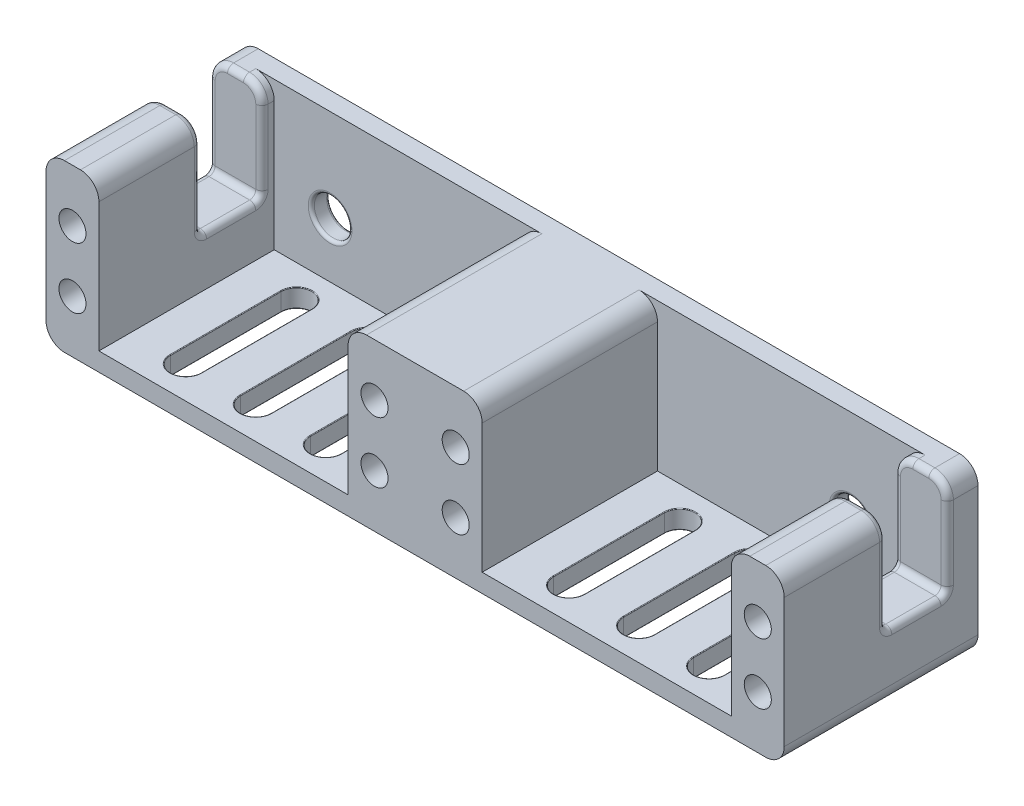
SolidWorks part; units mm, degrees
ref_plane "Front Plane" through (0, 0, 0) normal (0, 0, 1) x (1, 0, 0)
ref_plane "Top Plane" through (0, 0, 0) normal (0, 1, 0) x (1, 0, 0)
ref_plane "Right Plane" through (0, 0, 0) normal (1, 0, 0) x (0, 0, -1)
sketch "Sketch1" plane through (0, 0, 0) normal (0, 1, 0) x (1, 0, 0)
  line L0 (0, 0) -> (60, 0)
  line L6 (60, -31.5) -> (0, -31.5)
  line L7 (0, -31.5) -> (0, -26.5)
  line L9 (0, -26.5) -> (0, -3)
  line L11 (0, -3) -> (0, 0)
  line L12 (60, 0) -> (60, -31.5)
  dimension "D1" = 23.5
  dimension "D2" = 5
  dimension "D3" = 60
  dimension "D4" = 31.5
  dimension "D6" = 3
extrude "Boss-Extrude1" add sketch "Sketch1" along normal blind 27
sketch "Sketch2" plane through (0, 0, 31.5) normal (0, 0, 1) x (1, 0, 0)
  line L0 (0, 27) -> (0, 0) construction
  line L1 (0, 13.5) -> (60, 13.5) construction
  line L3 (60, 27) -> (60, 0) construction
  circle A0 centre (4.3, 18.45) radius 2.2
  circle A1 centre (4.3, 8.55) radius 2.2
  circle A2 centre (53.4, 18.45) radius 2.2
  circle A3 centre (53.4, 8.55) radius 2.2
  point P10 (28.85, 13.5)
  dimension "D1" = 4.3
  dimension "D2" = 4.4
  dimension "D3" = 9.9
  dimension "D4" = 4.95
  dimension "D8" = 4.4
  dimension "D9" = 9.9
  dimension "D10" = 49.1
  dimension "D11" = 4.95
  dimension "D12" = 4.4
extrude "Cut-Extrude1" cut sketch "Sketch2" against normal blind 5
sketch "Sketch4" plane through (0, 0, 31.5) normal (0, 0, 1) x (1, 0, 0)
  line L0 (49.1, 3) -> (8.6, 3)
  line L1 (49.1, 3) -> (49.1, 24)
  line L2 (49.1, 24) -> (8.6, 24)
  line L3 (8.6, 3) -> (8.6, 24)
  line L4 (0, 13.5) -> (60, 13.5) construction
  line L5 (0, 27) -> (0, 0) construction
  line L6 (60, 27) -> (60, 0) construction
  line L7 (8.6, 13.5) -> (49.1, 13.5) construction
  circle A0 centre (4.3, 18.45) radius 2.2 construction
  dimension "D1" = 4.3
  dimension "D2" = 40.5
  dimension "D3" = 21
extrude "Cut-Extrude2" cut sketch "Sketch4" against normal blind 28.5
sketch "Sketch5" plane through (0, 0, 31.5) normal (0, 0, 1) x (1, 0, 0)
  line L0 (8.6, 24) -> (8.6, 27)
  line L1 (8.6, 24) -> (49.1, 24)
  line L2 (8.6, 27) -> (49.1, 27)
  line L3 (49.1, 24) -> (49.1, 27)
  line L4 (0, 27) -> (60, 27) construction
  line L5 (49.1, 3) -> (49.1, 24) construction
  line L6 (49.1, 3) -> (49.1, 24) construction
extrude "Cut-Extrude4" cut sketch "Sketch5" against normal blind 28.5
sketch "Sketch10" plane through (0, 3, 0) normal (0, 1, 0) x (1, 0, 0)
  line L0 (28.85, -3) -> (28.85, -31.5) construction
  line L1 (49.1, -3) -> (8.6, -3) construction
  line L2 (8.6, -31.5) -> (49.1, -31.5) construction
  line L3 (8.6, -17.25) -> (49.1, -17.25) construction
  line L4 (8.6, -3) -> (8.6, -31.5) construction
  line L5 (49.1, -3) -> (49.1, -31.5) construction
  line L6 (28.85, -17.25) -> (26.35, -26.25) construction
  line L8 (31.35, -26.25) -> (31.35, -8.25)
  line L10 (26.35, -26.25) -> (26.35, -8.25)
  line L11 (28.85, -17.25) -> (26.35, -8.25) construction
  line L12 (31.35, -8.25) -> (28.85, -17.25) construction
  line L13 (31.35, -26.25) -> (28.85, -17.25) construction
  line L14 (42.73, -26.25) -> (42.73, -8.25)
  line L15 (37.73, -26.25) -> (37.73, -8.25)
  line L16 (40.23, -5.75) -> (40.23, -28.75) construction
  line L17 (19.97, -26.25) -> (19.97, -8.25)
  line L18 (14.97, -26.25) -> (14.97, -8.25)
  arc A0 (31.35, -8.25) -> (26.35, -8.25) centre (28.85, -8.25) ccw
  arc A1 (31.35, -26.25) -> (26.35, -26.25) centre (28.85, -26.25) cw
  arc A2 (42.73, -8.25) -> (37.73, -8.25) centre (40.23, -8.25) ccw
  arc A3 (42.73, -26.25) -> (37.73, -26.25) centre (40.23, -26.25) cw
  arc A4 (14.97, -26.25) -> (19.97, -26.25) centre (17.47, -26.25) ccw
  arc A5 (14.97, -8.25) -> (19.97, -8.25) centre (17.47, -8.25) cw
  point P12 (28.85, -17.25)
  point P20 (31.35, -17.25)
  point P22 (26.35, -17.25)
  dimension "D3" = 2.5
  dimension "D1" = 5
  dimension "D2" = 18
  dimension "D5" = 11.38
  dimension "D4" = 2
extrude "Cut-Extrude7" cut sketch "Sketch10" along direction (0, -1, 0) on the side against the normal up to surface (3 mm away) up to face at (30, 0, 15.75)
sketch "Sketch6" plane through (8.6, 0, 0) normal (1, 0, 0) x (0, 0, -1)
  line L5 (-15, 27) -> (-5, 27)
  line L6 (-15, 27) -> (-15, 11)
  line L7 (-5, 27) -> (-5, 11)
  line L8 (-15, 11) -> (-5, 11)
  line L9 (-3, 27) -> (-31.5, 27) construction
  line L10 (-3, 27) -> (-3, 3) construction
  line L11 (-31.5, 15) -> (-3, 15) construction
  line L12 (-31.5, 27) -> (-31.5, 3) construction
  dimension "D3" = 2
  dimension "D4" = 10
  dimension "D5" = 4
extrude "Cut-Extrude5" cut sketch "Sketch6" against normal blind 28.5
fillet "Fillet1" radius 3 6 edges at (0, 0, 15.75) (0, 27, 2.5) (8.6, 27, 4) (0, 27, 23.25) (8.6, 27, 23.25) (49.1, 27, 17.25)
sketch "Sketch11" plane through (0, 0, 31.5) normal (0, 0, 1) x (1, 0, 0)
  line L0 (60, 13.5) -> (49.1, 13.5) construction
  line L1 (60, 27) -> (60, 0) construction
  line L2 (49.1, 3) -> (49.1, 24) construction
  line L3 (60, 24) -> (60, 3)
  line L4 (60, 24) -> (58.5, 24)
  line L5 (60, 3) -> (58.5, 3)
  line L6 (58.5, 24) -> (58.5, 3)
  line L7 (52.1, 27) -> (60, 27) construction
  point P6 (58.5, 13.5)
  dimension "D1" = 3
  dimension "D2" = 1.5
fillet "Fillet2" radius 1 14 edges at (4.3, 11, 5) (4.3, 11, 15) (4.3, 27, 15) (7.7213, 26.1213, 15) (0.8787, 26.1213, 15) (8.6, 17.5, 15) (0, 17.5, 15) (8.6, 11, 10) (0, 11, 10) (8.6, 17.5, 5) (7.7213, 26.1213, 5) (4.3, 27, 5) (0.8787, 26.1213, 5) (0, 17.5, 5)
sketch "Sketch9" plane through (0, 0, 0) normal (0, 0, -1) x (-1, 0, 0)
  line L0 (0, 12) -> (-58.987, 12) construction
  line L1 (0, 24) -> (0, 3) construction
  circle A0 centre (-17.68, 12) radius 3.05
  dimension "D1" = 17.68
  dimension "D2" = 6.1
extrude "Cut-Extrude6" cut sketch "Sketch9" against normal blind 10
fillet "Fillet3" radius 0.5 2 edges at (20.73, 12, 3) (14.63, 12, 0)
sketch "Sketch12" plane through (0, 0, 0) normal (0, 0, -1) x (-1, 0, 0)
  line L0 (-60, 13.5) -> (0, 13.5) construction
  line L1 (-60, 27) -> (-60, 0) construction
  line L2 (0, 24) -> (0, 3) construction
  line L3 (-60, 15) -> (-35, 15)
  line L5 (-35, 12) -> (-60, 12)
  line L6 (-60, 12) -> (-60, 15)
  line L7 (-60, 7.5) -> (-35, 7.5)
  line L8 (-60, 4.5) -> (-60, 7.5)
  line L9 (-35, 4.5) -> (-60, 4.5)
  line L10 (-60, 6) -> (-33.5, 6) construction
  line L13 (-60, 22.5) -> (-60, 19.5)
  line L14 (-35, 22.5) -> (-60, 22.5)
  line L15 (-60, 19.5) -> (-35, 19.5)
  arc A0 (-35, 12) -> (-35, 15) centre (-35, 13.5) ccw
  arc A1 (-35, 4.5) -> (-35, 7.5) centre (-35, 6) ccw
  arc A2 (-35, 22.5) -> (-35, 19.5) centre (-35, 21) cw
  point P23 (-60, 21)
  dimension "D2" = 25
  dimension "D1" = 3
  dimension "D4" = 7.5
  dimension "D3" = 2
extrude "Cut-Extrude8" cut sketch "Sketch12" against normal blind 0.1
fillet "Fillet4" radius 0.1 33 edges at (47.5, 4.5, 0) (33.5, 6, 0) (47.5, 12, 0) (33.5, 13.5, 0) (47.5, 19.5, 0) (33.5, 21, 0) (47.5, 7.5, 0) (47.5, 15, 0) (47.5, 22.5, 0) (14.97, 3, 17.25) (17.47, 3, 5.75) (19.97, 3, 17.25) (26.35, 3, 17.25) (28.85, 3, 5.75) (31.35, 3, 17.25) (37.73, 3, 17.25) (40.23, 3, 5.75) (42.73, 3, 17.25) (40.23, 0, 5.75) (42.73, 0, 17.25) (40.23, 0, 28.75) (26.35, 0, 17.25) (28.85, 0, 5.75) (31.35, 0, 17.25) (17.47, 0, 28.75) (14.97, 0, 17.25) (17.47, 0, 5.75) (17.47, 3, 28.75) (28.85, 3, 28.75) (40.23, 3, 28.75) (37.73, 0, 17.25) (28.85, 0, 28.75) (19.97, 0, 17.25)
mirror "Mirror1" about plane through (60, 27, 0) normal (-1, 0, 0) of bodies 113 103
other "Flex1" [suppressed] parameters "D0"=15, "D1"=56, "D2"=56
